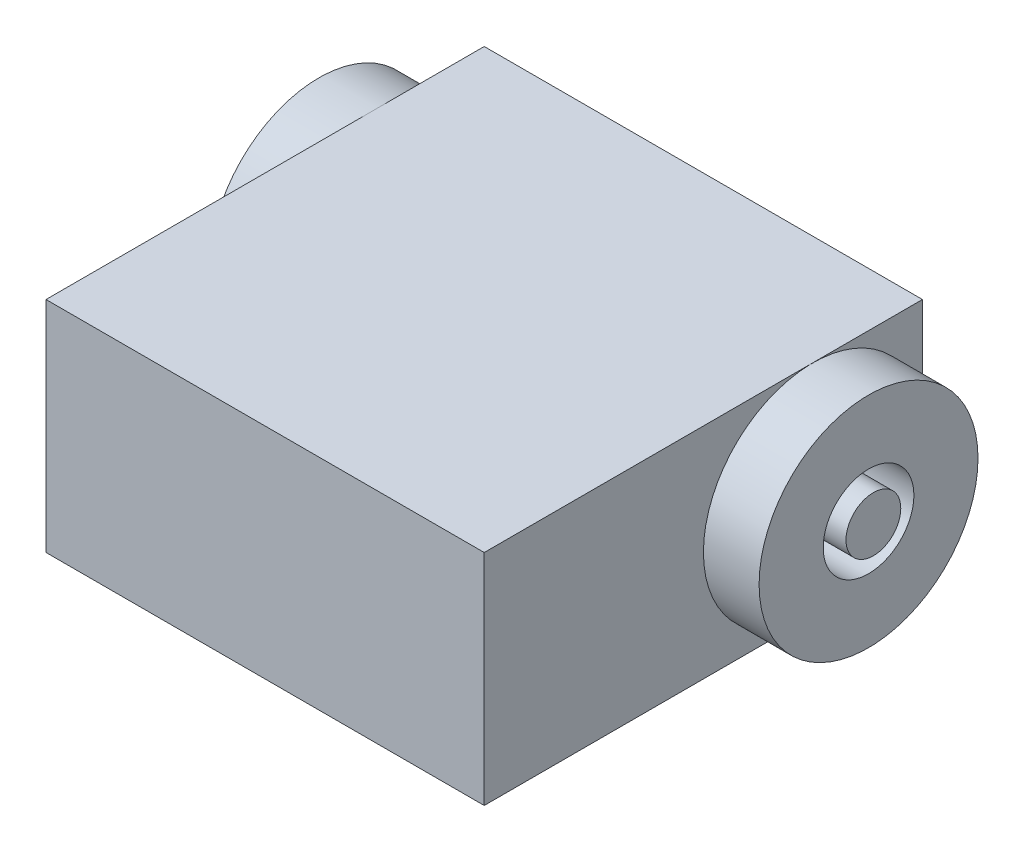
SolidWorks part; units mm, degrees
ref_plane "Front Plane" through (0, 0, 0) normal (0, 0, 1) x (1, 0, 0)
ref_plane "Top Plane" through (0, 0, 0) normal (0, 1, 0) x (1, 0, 0)
ref_plane "Right Plane" through (0, 0, 0) normal (1, 0, 0) x (0, 0, -1)
sketch "Sketch1" plane through (0, 0, 0) normal (0, 1, 0) x (1, 0, 0)
  line L1 (-20, -20) -> (20, -20)
  line L2 (-20, -20) -> (-20, 20)
  line L3 (-20, 20) -> (20, 20)
  line L4 (20, -20) -> (20, 20)
  point P7 (-20, 0)
  point P9 (20, 0)
  point P10 (0, 20)
  dimension "D1" = 40
  dimension "D2" = 40
extrude "Boss-Extrude1" add sketch "Sketch1" along normal blind 20
sketch "Sketch2" plane through (20, 0, 0) normal (1, 0, 0) x (0, 0, -1)
  line L1 (20, 10) -> (0, 10) construction
  line L2 (20, 20) -> (20, 0) construction
  line L4 (20, 20) -> (10, 20) construction
  line L5 (20, 20) -> (20, 10) construction
  line L6 (20, 10) -> (10, 10) construction
  line L7 (10, 20) -> (10, 10) construction
  circle A0 centre (10, 10) radius 2.5
  dimension "D1" = 5
extrude "Boss-Extrude2" add sketch "Sketch2" along normal blind 5.522
mirror "Mirror1" about plane through (0, 0, 0) normal (1, 0, 0) of "Boss-Extrude2"
sketch "Sketch3" plane through (0, 20, 0) normal (0, 1, 0) x (1, 0, 0)
  line L1 (-20.717, -1.2636) -> (-22.717, -1.2636)
  line L2 (-20.717, -1.2636) -> (-20.717, -21.7623)
  line L4 (-22.717, -1.2636) -> (-22.717, -23.7623)
  line L6 (-20.717, -21.7623) -> (21.4471, -21.7623)
  line L8 (-22.717, -23.7623) -> (23.4471, -23.7623)
  line L11 (23.4471, -23.7623) -> (23.4471, -1.8252)
  line L12 (23.4471, -1.8252) -> (21.4471, -1.8252)
  line L13 (21.4471, -21.7623) -> (21.4471, -1.8252)
  dimension "D1" = 2
  dimension "D2" = 2
  dimension "D3" = 2
extrude "Boss-Extrude3" [suppressed] add sketch "Sketch3" against normal up to surface (20 mm away)
sketch "Sketch4" plane through (0, 20, 0) normal (0, 1, 0) x (1, 0, 0)
  line L0 (20, 20) -> (-20, 20) construction
  line L1 (-30.1617, -0.4159) -> (-32.1617, -0.4159)
  line L2 (-30.1617, -0.4159) -> (-30.1617, 35)
  line L3 (-27.6801, 37) -> (-32.1617, 37)
  line L4 (-32.1617, -0.4159) -> (-32.1617, 37)
  line L5 (-32.1617, 37) -> (33.0115, 37)
  line L6 (-32.1617, 37) -> (-32.1617, 32.93)
  line L7 (-30.1617, 35) -> (31.0115, 35)
  line L8 (33.0115, 37) -> (33.0115, 32.93)
  line L9 (33.0115, 37) -> (31.0115, 37)
  line L10 (33.0115, 37) -> (33.0115, -0.4159)
  line L11 (33.0115, -0.4159) -> (31.0115, -0.4159)
  line L12 (31.0115, 35) -> (31.0115, -0.4159)
  dimension "D1" = 2
  dimension "D2" = 2
  dimension "D3" = 2
  dimension "D4" = 15
extrude "Boss-Extrude4" [suppressed] add sketch "Sketch4" against normal up to vertex separate body contours L7 L12 L11 L10 L8 L5 L3 L4 L1 L2
ref_axis "Axis1" through (45.4174, 10, -10) along (-1, 0, 0)
ref_plane "Plane1" through (0, 10, 0) normal (0, 1, 0) x (1, 0, 0)
ref_plane "Plane2" through (0, 10, 0) normal (0, 1, 0) x (1, 0, 0)
sketch "Sketch5" plane through (20, 0, 0) normal (1, 0, 0) x (0, 0, -1)
  circle A0 centre (10, 10) radius 4.1409
  circle A1 centre (10, 10) radius 9.991
extrude "Boss-Extrude5" add sketch "Sketch5" along normal blind 5.08
mirror "Mirror2" about plane through (0, 0, 0) normal (1, 0, 0) of "Boss-Extrude5"
